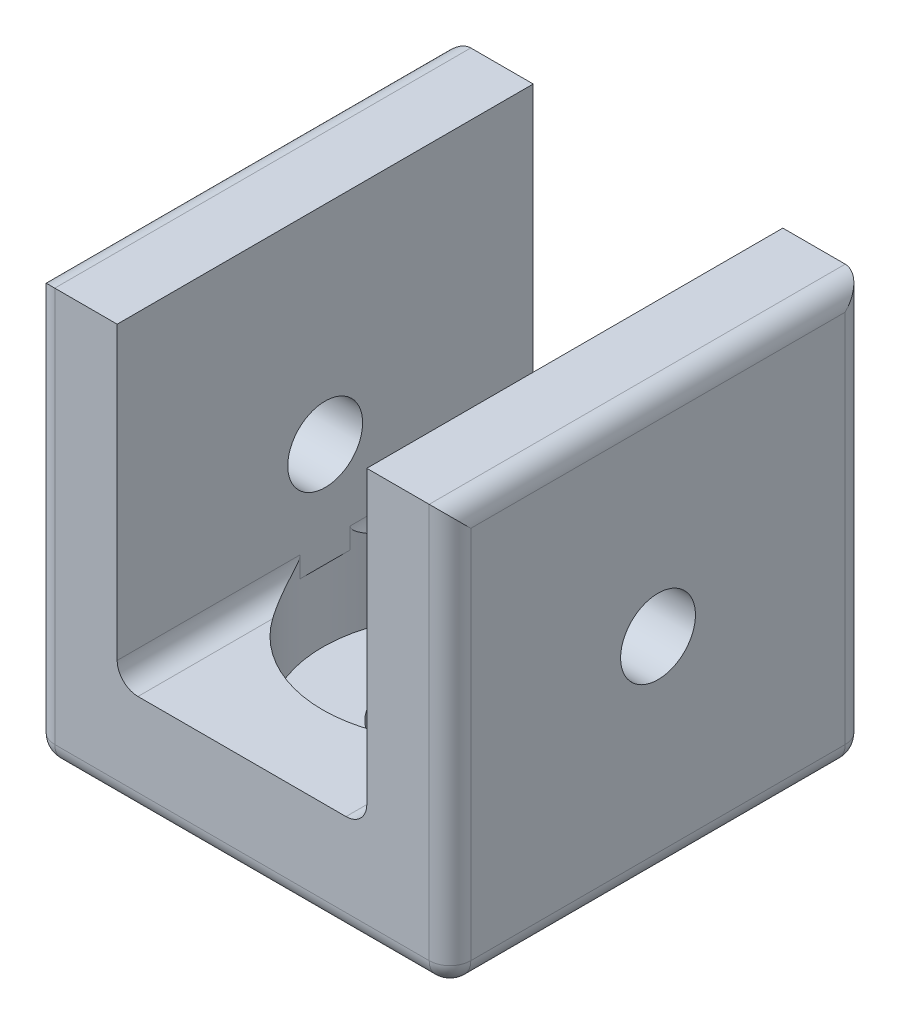
SolidWorks part; units mm, degrees
material "ABS"
ref_plane "Front Plane" through (0, 0, 0) normal (0, 0, 1) x (1, 0, 0)
ref_plane "Top Plane" through (0, 0, 0) normal (0, 1, 0) x (1, 0, 0)
ref_plane "Right Plane" through (0, 0, 0) normal (1, 0, 0) x (0, 0, -1)
sketch "Sketch1" plane through (0, 0, 0) normal (0, 0, 1) x (1, 0, 0)
  line L0 (0, 0) -> (20, 0)
  line L1 (20, 0) -> (20, 20)
  line L2 (20, 20) -> (16, 20)
  line L3 (16, 20) -> (16, 5)
  line L4 (16, 5) -> (4, 5)
  line L5 (4, 5) -> (4, 20)
  line L6 (4, 20) -> (0, 20)
  line L7 (0, 20) -> (0, 0)
  dimension "D1" = 20
  dimension "D2" = 20
  dimension "D3" = 5
  dimension "D4" = 4
extrude "Boss-Extrude1" add sketch "Sketch1" along normal blind 20
sketch "Sketch2" plane through (0, 0, 0) normal (0, -1, 0) x (1, 0, 0)
  line L0 (10, -1000) -> (10, 49000) construction
  line L1 (0, 0) -> (20, 0) construction
  circle A0 centre (10, 10) radius 2.5
  point P3 (0, 0)
  point P7 (10, 0)
  point P8 (0, 0)
  dimension "D2" = 5
  dimension "D1" = 10
extrude "Cut-Extrude1" cut sketch "Sketch2" against normal blind 20
sketch "Sketch3" plane through (0, 0, 0) normal (0, -1, 0) x (-1, 0, 0)
  point P0 (-10, -10)
sketch "Sketch5" plane through (0, 5, 0) normal (0, 1, 0) x (1, 0, 0)
  point P0 (10, -10)
hole_wizard "CBORE for M5 Hex Head Screw2" positions "Sketch5" profile "Sketch6" counterbore size "M5" standard "ISO"
sketch "Sketch6" plane through (10, 5, 10) normal (1, 0, 0) x (0, 0, 1)
  line L0 (0, 0) -> (0, 41.7425)
  line L1 (0, 41.7425) -> (2.9, 40)
  line L2 (2.9, 40) -> (2.9, 3.5)
  line L3 (2.9, 3.5) -> (6.119, 3.5)
  line L4 (6.119, 3.5) -> (6.119, 0)
  line L5 (6.119, 0) -> (0, 0)
  line L10 (0, 41.7425) -> (-2.9, 40) construction
  line L11 (0, -6.35) -> (0, 107.95) construction
  dimension "Hole Dia." = 5.8
  dimension "Hole Depth" = 40
  dimension "C'Bore Dia." = 12.238
  dimension "C'Bore Depth" = 3.5
  dimension "Drill Angle" = 118
sketch "Sketch7" plane through (0, 0, 0) normal (-1, 0, 0) x (0, 0, 1)
  line L0 (20, 20) -> (20, 0) construction
  line L1 (20, 0) -> (0, 0) construction
  circle A0 centre (10, 10) radius 1.4562
  point P0 (10, 10)
  dimension "D1" = 10
  dimension "D2" = 10
hole_wizard "M3 Clearance Hole1" positions "Sketch7" profile "Sketch8" hole size "M3" standard "ANSI Metric" end condition through all
sketch "Sketch8" plane through (0, 10, 10) normal (0, 1, 0) x (0, 0, 1)
  line L0 (0, 0) -> (0, 20)
  line L1 (0, 20) -> (1.8, 20)
  line L2 (1.8, 20) -> (1.8, 0)
  line L5 (1.8, 0) -> (0, 0)
  line L11 (0, -6.35) -> (0, 107.95) construction
  dimension "Thru Hole Dia." = 3.6
  dimension "Thru Hole Depth" = 20
fillet "Fillet1" radius 1 14 edges at (4, 5, 4.3995) (4, 5, 15.6005) (16, 5, 15.6005) (16, 5, 4.3995) (20, 20, 10) (20, 10, 20) (20, 10, 0) (10, 0, 0) (20, 0, 10) (10, 0, 20) (0, 0, 10) (0, 10, 0) (0, 20, 10) (0, 10, 20)
